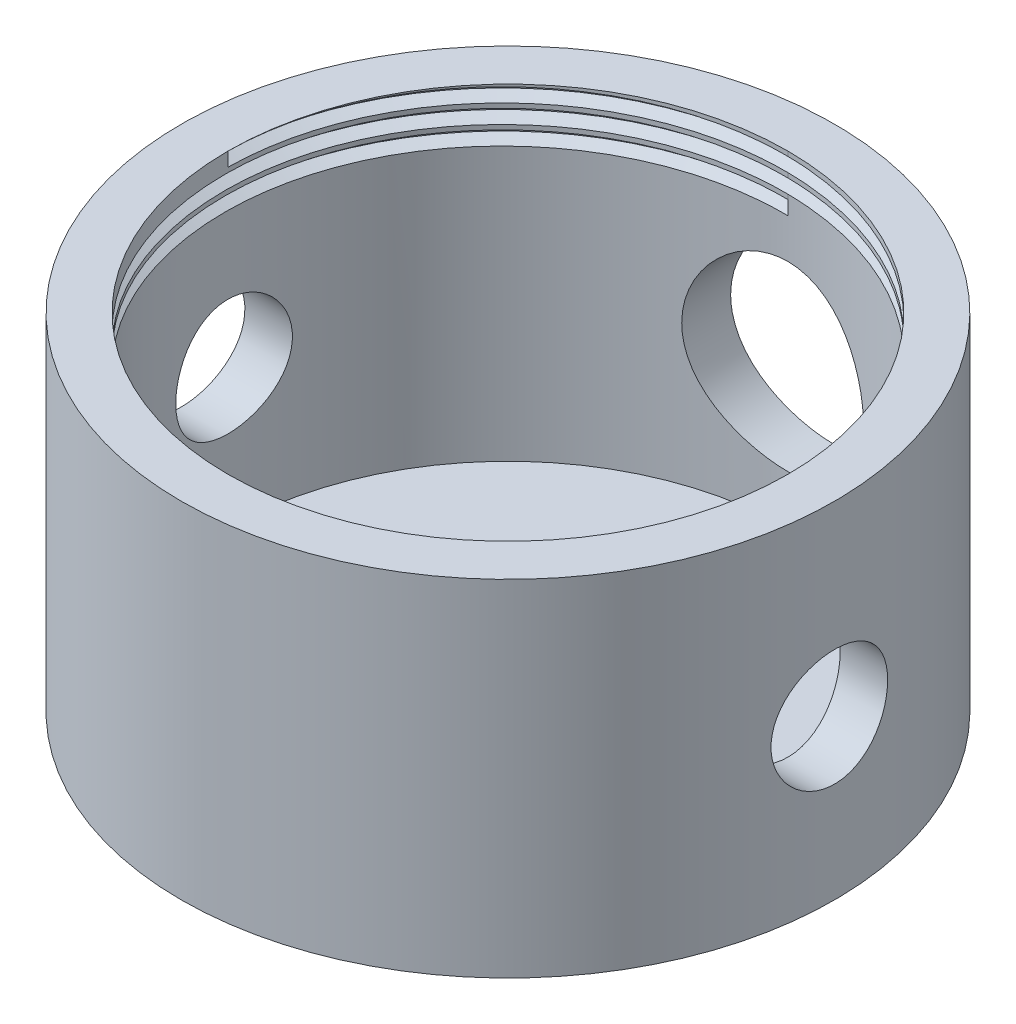
SolidWorks part; units mm, degrees
ref_plane "Front Plane" through (0, 0, 0) normal (0, 0, 1) x (1, 0, 0)
ref_plane "Top Plane" through (0, 0, 0) normal (0, 1, 0) x (1, 0, 0)
ref_plane "Right Plane" through (0, 0, 0) normal (1, 0, 0) x (0, 0, -1)
sketch "Sketch1" plane through (0, 0, 0) normal (0, 1, 0) x (1, 0, 0)
  circle A0 centre (0, 0) radius 35
  dimension "D1" = 70
extrude "Boss-Extrude1" add sketch "Sketch1" along normal blind 2 contours A0
sketch "Sketch2" plane through (0, 2, 0) normal (0, 1, 0) x (1, 0, 0)
  circle A0 centre (0, 0) radius 35
  circle A1 centre (0, 0) radius 30
  dimension "D1" = 70
  dimension "D2" = 5
extrude "Boss-Extrude2" add sketch "Sketch2" along normal blind 35
ref_plane "Plane3" through (0, 0, 40) normal (0, 0, 1) x (1, 0, 0)
sketch "Sketch5" plane through (0, 0, 40) normal (0, 0, 1) x (1, 0, 0)
  line L0 (-35, 0) -> (35, 0) construction
  line L1 (-26.6422, 0) -> (27.3578, 0)
  line L2 (-26.6422, 0) -> (-26.6422, -34)
  line L3 (-26.6422, -34) -> (27.3578, -34)
  line L4 (27.3578, 0) -> (27.3578, -34)
  line L5 (-35, 0) -> (35, 0) construction
  line L6 (-24.6422, -2) -> (25.3578, -2)
  line L7 (-24.6422, -2) -> (-24.6422, -32)
  line L8 (-24.6422, -32) -> (25.3578, -32)
  line L9 (25.3578, -2) -> (25.3578, -32)
  dimension "D1" = 2
  dimension "D2" = 2
  dimension "D3" = 2
  dimension "D4" = 2
  dimension "D5" = 50
  dimension "D6" = 2
  dimension "D7" = 30
thread "Thread1" pitch 2 method cut profile "Thread Profile1" start angle 0, offset 0, length 4.5, pitch 2, diameter 60
ref_plane "Plane4" through (-30, 37, 0) normal (0, 0, 1) x (-1, 0, 0)
sketch "Thread Profile1" plane through (-30, 37, 0) normal (0, 0, 1) x (-1, 0, 0)
  line L0 (0, 0) -> (0, 2) construction
  line L1 (0, 0) -> (1.0825, 0.625)
  line L2 (1.0825, 0.625) -> (1.0825, 0.875)
  line L3 (1.0825, 0.875) -> (0, 1.5)
  line L4 (1.0825, 0.75) -> (0, 0.75) construction
  line L11 (0, 0) -> (0, 1.5)
  point P2 (0, 0)
  dimension "Pitch" = 2
  dimension "Profile_Angle" = 60
  dimension "Profile_Land" = 0.25
  dimension "Profile_Height" = 1.0825
ref_plane "Plane6" through (0, 0, -35) normal (0, 0, -1) x (-1, 0, 0)
sketch "Sketch10" plane through (0, 0, -35) normal (0, 0, -1) x (-1, 0, 0)
  line L0 (0, 17) -> (-42.3594, 17) construction
  line L1 (0, 37) -> (0, 0) construction
  line L2 (35, 37) -> (-35, 37) construction
  line L3 (-42.3594, 17) -> (37.1989, 17) construction
  circle A1 centre (0, 17) radius 9.75
  dimension "D2" = 19.5
  dimension "D5" = 37
  dimension "D6" = 20
extrude "Cut-Extrude2" cut sketch "Sketch10" against normal up to next
ref_plane "Plane8" through (-35, 0, 0) normal (-1, 0, 0) x (0, 0, 1)
sketch "Sketch12" plane through (-35, 0, 0) normal (-1, 0, 0) x (0, 0, 1)
  line L1 (35, 37) -> (-35, 37) construction
  circle A0 centre (0, 17) radius 6.25
  dimension "D1" = 12.5
  dimension "D2" = 20
extrude "Cut-Extrude4" cut sketch "Sketch12" against normal up to next
ref_plane "Plane9" through (35, 0, 0) normal (1, 0, 0) x (0, 0, -1)
sketch "Sketch13" plane through (35, 0, 0) normal (1, 0, 0) x (0, 0, -1)
  line L0 (35, 37) -> (-35, 37) construction
  circle A0 centre (0, 17) radius 6.25
  dimension "D1" = 12.5
  dimension "D2" = 20
extrude "Cut-Extrude5" cut sketch "Sketch13" against normal up to next
sketch "Sketch14" plane through (0, 2, 0) normal (0, 1, 0) x (1, 0, 0)
  circle A0 centre (0, 0) radius 5
  dimension "D1" = 10
extrude "Cut-Extrude6" cut sketch "Sketch14" against normal up to next
